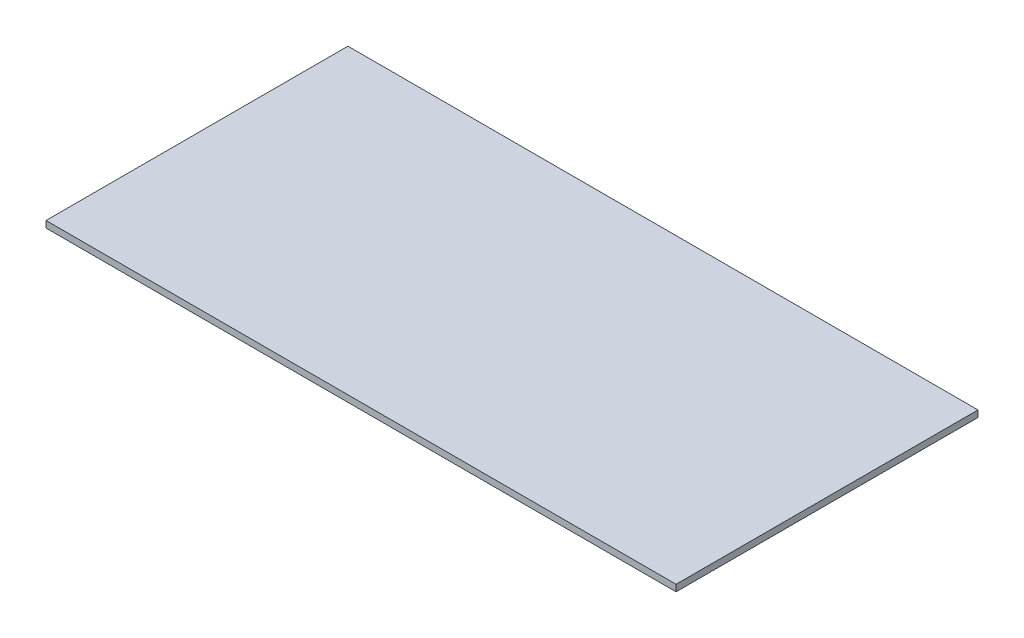
SolidWorks part; units mm, degrees
material "Acrylic (Medium-high impact)"
ref_plane "Front Plane" through (0, 0, 0) normal (0, 0, 1) x (1, 0, 0)
ref_plane "Top Plane" through (0, 0, 0) normal (0, 1, 0) x (1, 0, 0)
ref_plane "Right Plane" through (0, 0, 0) normal (1, 0, 0) x (0, 0, -1)
sketch "Sketch1" plane through (0, 0, 0) normal (0, 1, 0) x (1, 0, 0)
  line L1 (-304.8, -146.05) -> (304.8, -146.05)
  line L2 (-304.8, -146.05) -> (-304.8, 146.05)
  line L3 (-304.8, 146.05) -> (304.8, 146.05)
  line L4 (304.8, -146.05) -> (304.8, 146.05)
  line L5 (-304.8, -146.05) -> (304.8, 146.05) construction
  line L6 (-304.8, 146.05) -> (304.8, -146.05) construction
  point P0 (0, 0)
  dimension "D1" = 609.6
  dimension "D2" = 292.1
extrude "Boss-Extrude1" add sketch "Sketch1" along normal mid plane 6.35
sketch "Sketch2" plane through (0, 3.175, 0) normal (0, 1, 0) x (1, 0, 0)
  line L0 (304.8, -146.05) -> (304.8, 146.05) construction
  line L1 (-304.8, -146.05) -> (304.8, -146.05) construction
  line L2 (304.8, 146.05) -> (-304.8, 146.05) construction
  line L3 (-304.8, 146.05) -> (-304.8, -146.05) construction
  line L4 (304.8, -146.05) -> (304.8, 146.05) construction
  line L5 (-304.8, -146.05) -> (304.8, -146.05) construction
  line L6 (304.8, 146.05) -> (-304.8, 146.05) construction
  line L7 (-304.8, 146.05) -> (-304.8, -146.05) construction
  line L8 (-304.8, 146.05) -> (-304.8, -146.05)
  line L9 (-304.8, -146.05) -> (-152.4, -146.05)
  line L10 (-152.4, -146.05) -> (-152.4, 146.05)
  line L11 (-152.4, 146.05) -> (-304.8, 146.05)
  dimension "D1" = 152.4
extrude "Cut-Extrude1" [suppressed] cut sketch "Sketch2" against normal through all both and the other way through all
